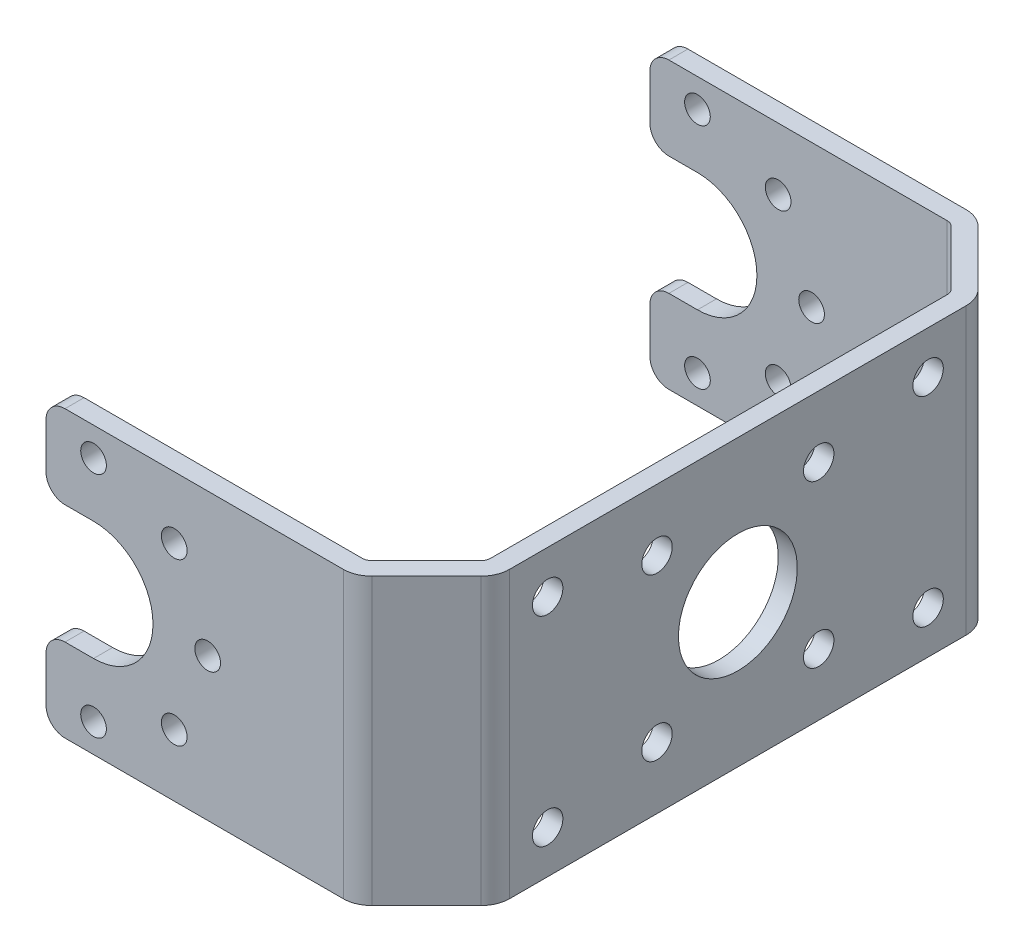
SolidWorks part; units mm, degrees
ref_plane "前视基准面" through (0, 0, 0) normal (0, 0, 1) x (1, 0, 0)
ref_plane "上视基准面" through (0, 0, 0) normal (0, 1, 0) x (1, 0, 0)
ref_plane "右视基准面" through (0, 0, 0) normal (1, 0, 0) x (0, 0, -1)
sketch "草图1" plane through (0, 0, 0) normal (0, 1, 0) x (1, 0, 0)
  line L0 (0, 0) -> (-58.3043, 0) construction
  line L1 (0, 0) -> (0, 25.2484)
  line L2 (0, 25.2484) -> (-7.5016, 32.75)
  line L3 (-7.5016, 32.75) -> (-40, 32.75)
  line L4 (-2, 0) -> (-2, 24.42)
  line L5 (-2, 24.42) -> (-8.33, 30.75)
  line L6 (-8.33, 30.75) -> (-40, 30.75)
  line L7 (-40, 32.75) -> (-40, 30.75)
  line L8 (-40, -32.75) -> (-40, -30.75)
  line L9 (-8.33, -30.75) -> (-40, -30.75)
  line L10 (-2, -24.42) -> (-8.33, -30.75)
  line L11 (-2, 0) -> (-2, -24.42)
  line L12 (-7.5016, -32.75) -> (-40, -32.75)
  line L13 (0, -25.2484) -> (-7.5016, -32.75)
  line L14 (0, 0) -> (0, -25.2484)
  dimension "D1" = 2
  dimension "D2" = 48.84
  dimension "D3" = 135
  dimension "D4" = 61.5
  dimension "D5" = 40
extrude "凸台-拉伸1" add sketch "草图1" along normal mid plane 30
sketch "草图2" plane through (-2, 0, 0) normal (-1, 0, 0) x (0, 0, 1)
  line L1 (-8.5, -8.5) -> (8.5, -8.5) construction
  line L2 (-8.5, -8.5) -> (-8.5, 8.5) construction
  line L3 (-8.5, 8.5) -> (8.5, 8.5) construction
  line L4 (8.5, -8.5) -> (8.5, 8.5) construction
  line L5 (-8.5, -8.5) -> (8.5, 8.5) construction
  line L6 (-8.5, 8.5) -> (8.5, -8.5) construction
  line L7 (-20, -10.5) -> (20, -10.5) construction
  line L8 (-20, -10.5) -> (-20, 10.5) construction
  line L9 (-20, 10.5) -> (20, 10.5) construction
  line L10 (20, -10.5) -> (20, 10.5) construction
  line L11 (-20, -10.5) -> (20, 10.5) construction
  line L12 (-20, 10.5) -> (20, -10.5) construction
  circle A1 centre (-20, 10.5) radius 1.6
  circle A2 centre (-8.5, 8.5) radius 1.6
  circle A3 centre (8.5, 8.5) radius 1.6
  circle A4 centre (20, 10.5) radius 1.6
  circle A5 centre (20, -10.5) radius 1.6
  circle A6 centre (8.5, -8.5) radius 1.6
  circle A7 centre (-8.5, -8.5) radius 1.6
  circle A8 centre (-20, -10.5) radius 1.6
  circle A9 centre (0, 0) radius 6.25
  point P0 (0, 0)
  point P7 (0, 0)
  dimension "D5" = 3.2
  dimension "D6" = 12.5
  dimension "D1" = 17
  dimension "D2" = 17
  dimension "D3" = 21
  dimension "D4" = 40
extrude "切除-拉伸1" cut sketch "草图2" against normal up to surface (2 mm away) up to face at (0, 0, 0)
sketch "草图3" plane through (0, 0, 0) normal (0, 0, 1) x (1, 0, 0)
  line L0 (0, 0) -> (-35, 0) construction
  line L1 (-35, 6.25) -> (-40, 6.25)
  line L2 (-40, 15) -> (-40, -15) construction
  line L3 (-35, -6.25) -> (-40, -6.25)
  line L4 (-40, 6.25) -> (-40, -6.25)
  circle A0 centre (-35, 0) radius 12 construction
  arc A1 (-35, -6.25) -> (-35, 6.25) centre (-35, 0) ccw
  circle A2 centre (-23, 0) radius 1.35
  circle A3 centre (-26.5147, -8.4853) radius 1.35
  circle A4 centre (-35, -12) radius 1.35
  circle A5 centre (-43.4853, -8.4853) radius 1.35 [skipped]
  circle A6 centre (-47, 0) radius 1.35 [skipped]
  circle A7 centre (-43.4853, 8.4853) radius 1.35 [skipped]
  circle A8 centre (-35, 12) radius 1.35
  circle A9 centre (-26.5147, 8.4853) radius 1.35
  point P29 (-35, 0)
  dimension "D2" = 6.25
  dimension "D3" = 24
  dimension "D5" = 2.7
  dimension "D1" = 35
  dimension "D4" = 8
extrude "切除-拉伸2" cut sketch "草图3" against normal mid plane 74
fillet "圆角1" radius 2 8 edges at (-40, 15, -31.75) (-40, 6.25, -31.75) (-40, -6.25, -31.75) (-40, -15, -31.75) (-40, -15, 31.75) (-40, -6.25, 31.75) (-40, 6.25, 31.75) (-40, 15, 31.75)
fillet "圆角2" radius 1 4 edges at (-2, 0, 24.42) (-8.33, 0, 30.75) (-8.33, 0, -30.75) (-2, 0, -24.42)
fillet "圆角3" radius 3 4 edges at (0, 0, 25.2484) (-7.5016, 0, 32.75) (-7.5016, 0, -32.75) (0, 0, -25.2484)
